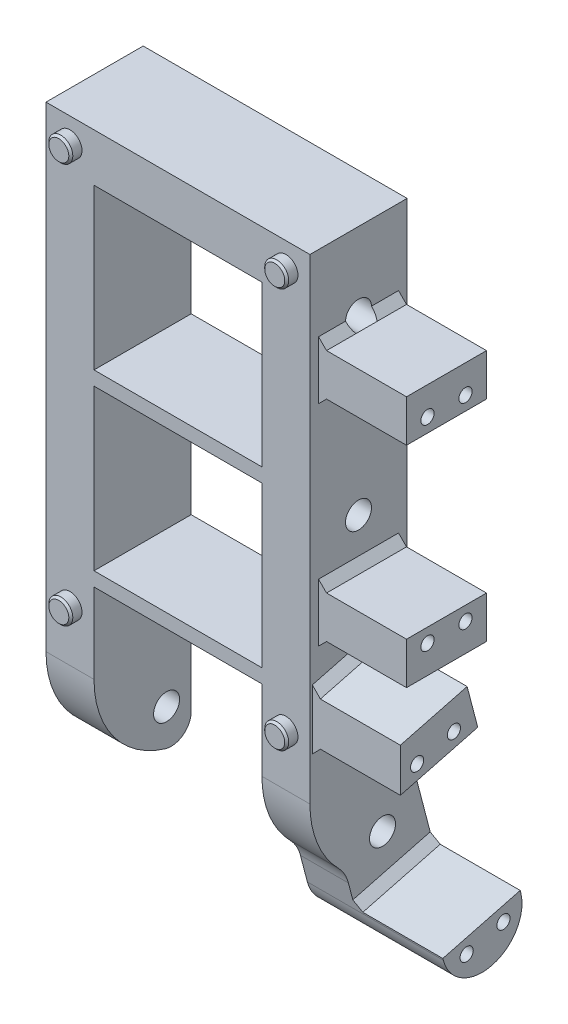
SolidWorks part; units mm, degrees
material "PBT General Purpose"
ref_plane "Front Plane" through (0, 0, 0) normal (0, 0, 1) x (1, 0, 0)
ref_plane "Top Plane" through (0, 0, 0) normal (0, 1, 0) x (1, 0, 0)
ref_plane "Right Plane" through (0, 0, 0) normal (1, 0, 0) x (0, 0, -1)
sketch "Sketch2" plane through (0, 0, 0) normal (0, 0, 1) x (1, 0, 0)
  line L0 (-33, 0) -> (33, 0)
  line L1 (33, 0) -> (33, -144)
  line L2 (33, -144) -> (21, -144)
  line L3 (21, -144) -> (21, -99)
  line L4 (21, -99) -> (-21, -99)
  line L5 (-21, -99) -> (-21, -144)
  line L6 (-21, -144) -> (-33, -144)
  line L7 (-33, -144) -> (-33, 0)
  line L8 (-21, -99) -> (-21, -95.5) construction
  line L9 (-21, -52) -> (21, -52)
  line L10 (-21, -52) -> (-21, -12)
  line L11 (-21, -12) -> (21, -12)
  line L12 (21, -52) -> (21, -12)
  line L13 (-21, -95.5) -> (21, -95.5)
  line L14 (-21, -95.5) -> (-21, -55.5)
  line L15 (-21, -55.5) -> (21, -55.5)
  line L16 (21, -95.5) -> (21, -55.5)
  line L17 (-21, -55.5) -> (-21, -52) construction
  line L18 (21, -52) -> (21, -55.5) construction
  line L19 (21, -95.5) -> (21, -99) construction
  dimension "D1" = 12
  dimension "D2" = 42
  dimension "D3" = 45
  dimension "D4" = 43.5
  dimension "D5" = 43.5
  dimension "D6" = 12
  dimension "D7" = 3.5
  dimension "D8" = 3.5
extrude "Boss-Extrude1" add sketch "Sketch2" along normal mid plane 24.3 contours L7 L0 L1 L2 L3 L4 L5 L6 | L10 L11 L12 L9 | L14 L15 L16 L13
sketch "Sketch3" plane through (0, 0, 0) normal (1, 0, 0) x (0, 0, -1)
  line L0 (-12.15, 0) -> (12.15, 0) construction
  circle A2 centre (0, -106) radius 3.25
  circle A3 centre (0, -62.5) radius 3.25
  circle A4 centre (0, -19) radius 3.25
  circle A5 centre (6, -134) radius 3.25
  dimension "D4" = 43.5
  dimension "D1" = 6.5
  dimension "D2" = 6.5
  dimension "D3" = 43.5
  dimension "D5" = 19
  dimension "D6" = 28
  dimension "D7" = 6
extrude "Cut-Extrude1" cut sketch "Sketch3" against normal through all both and the other way through all
fillet "Fillet1" radius 25 2 edges at (27, -144, 12.15) (-27, -144, 12.15)
fillet "Fillet2" radius 5 2 edges at (-27, -144, -12.15) (27, -144, -12.15)
sketch "Sketch4" plane through (0, 0, 12.15) normal (0, 0, -1) x (-1, 0, 0)
  line L5 (-33, -39.016) -> (-21, -39.016) construction
  line L6 (-27, -6) -> (27, -6) construction
  line L7 (-27, -6) -> (-27, -106) construction
  line L8 (-27, -106) -> (27, -106) construction
  line L9 (27, -6) -> (27, -106) construction
  line L10 (-33, 0) -> (-33, -138.1804) construction
  line L11 (-21, -52) -> (-21, -12) construction
  line L12 (0, -6) -> (0, 0) construction
  line L13 (33, 0) -> (-33, 0) construction
  line L14 (0, -6) -> (0, -12) construction
  line L15 (21, -12) -> (-21, -12) construction
  circle A0 centre (-27, -6) radius 3
  circle A1 centre (27, -6) radius 3
  circle A2 centre (27, -106) radius 3
  circle A3 centre (-27, -106) radius 3
  point P17 (-27, -39.016)
  dimension "D1" = 6
  dimension "D2" = 100
extrude "Boss-Extrude2" add sketch "Sketch4" against normal blind 2.8
chamfer "Chamfer1" distance 0.5 angle 45 4 edges at (-30, -106, 14.95) (24, -106, 14.95) (-30, -6, 14.95) (24, -6, 14.95)
ref_plane "Plane1" through (55, 0, 0) normal (1, 0, 0) x (0, 0, -1)
sketch "Sketch5" plane through (55, 0, 0) normal (1, 0, 0) x (0, 0, -1)
  line L0 (0, -62.5) -> (0, -76.89) construction
  line L1 (-4.75, -27.89) -> (4.75, -27.89) construction
  line L2 (-4.75, -27.89) -> (-4.75, -76.89) construction
  line L3 (-4.75, -76.89) -> (4.75, -76.89) construction
  line L4 (4.75, -27.89) -> (4.75, -76.89) construction
  line L5 (-7.3433, -101.7142) -> (5.0412, -149.1233) construction
  line L6 (-7.3433, -101.7142) -> (1.8483, -99.3131) construction
  line L7 (5.0412, -149.1233) -> (14.2328, -146.7223) construction
  line L8 (1.8483, -99.3131) -> (14.2328, -146.7223) construction
  line L9 (9.637, -147.9228) -> (6, -134) construction
  line L10 (12.15, 0) -> (12.15, -138.1804) construction
  circle A0 centre (6, -134) radius 3.25 construction
  point P11 (0, 0)
  point P14 (-7.8925, -103.9467)
  dimension "D1" = 9.5
  dimension "D2" = 49
  dimension "D3" = 14.39
  dimension "D4" = 165.36
sketch "Sketch6" plane through (55, 0, 0) normal (1, 0, 0) x (0, 0, -1)
  line L0 (4.75, -52.39) -> (-4.75, -52.39) construction
  line L1 (-10, -20.89) -> (10, -20.89)
  line L2 (-10, -20.89) -> (-10, -31.39)
  line L3 (-10, -31.39) -> (10, -31.39)
  line L4 (10, -20.89) -> (10, -31.39)
  line L5 (4.75, -27.89) -> (4.75, -76.89) construction
  line L6 (-4.75, -27.89) -> (-4.75, -76.89) construction
  line L7 (-10, -73.39) -> (10, -73.39)
  line L8 (10, -83.89) -> (10, -73.39)
  line L9 (-10, -83.89) -> (10, -83.89)
  line L10 (-10, -83.89) -> (-10, -73.39)
  line L12 (0, -62.5) -> (0, -76.89) construction
  line L13 (-4.75, -27.89) -> (4.75, -27.89) construction
  line L17 (-0.9229, -147.0639) -> (18.4277, -142.009)
  line L18 (1.7309, -157.223) -> (-0.9229, -147.0639)
  line L19 (1.7309, -157.223) -> (21.0815, -152.1681)
  line L21 (21.0815, -152.1681) -> (18.4277, -142.009)
  line L25 (9.637, -147.9228) -> (6, -134) construction
  line L26 (-1.151, -125.4188) -> (8.0405, -123.0177) construction
  line L27 (-7.3433, -101.7142) -> (5.0412, -149.1233) construction
  line L28 (1.8483, -99.3131) -> (14.2328, -146.7223) construction
  line L30 (-11.5382, -95.5752) -> (5.1586, -91.2135)
  line L31 (5.1586, -91.2135) -> (7.8124, -101.3726)
  line L32 (-11.5382, -106.4275) -> (7.8124, -101.3726)
  line L33 (-11.5382, -106.4275) -> (-11.5382, -95.5752)
  line L34 (5.0412, -149.1233) -> (14.2328, -146.7223) construction
  point P16 (0, -73.39)
  point P27 (8.7524, -144.5364)
  point P38 (-1.151, -149.0639)
  point P39 (18.4277, -144.009)
  point P40 (0, 0)
  point P41 (5.1586, -93.2135)
  point P42 (0, 0)
  dimension "D1" = 20
  dimension "D2" = 3.5
  dimension "D3" = 7
  dimension "D4" = 20
  dimension "D5" = 3.5
  dimension "D6" = 7
extrude "Boss-Extrude3" add sketch "Sketch6" against normal up to surface (22 mm away) up to face at (33, -134, -9.25)
sketch "Sketch8" plane through (33, 0, 0) normal (1, 0, 0) x (0, 0, -1)
  line L0 (-0.9229, -147.0639) -> (-3.2568, -138.1297)
  line L1 (12.15, 0) -> (12.15, -138.1804) construction
  line L2 (12.15, -117.9772) -> (12.15, -138.1804)
  line L3 (18.4277, -142.009) -> (12.15, -117.9772)
  line L4 (-0.9229, -147.0639) -> (1.7309, -157.223)
  line L5 (1.7309, -157.223) -> (21.0815, -152.1681)
  line L6 (21.0815, -152.1681) -> (18.4277, -142.009)
  line L7 (18.4277, -142.009) -> (-0.9229, -147.0639)
  line L8 (-0.9229, -147.0639) -> (1.7309, -157.223)
  line L9 (1.7309, -157.223) -> (21.0815, -152.1681)
  line L10 (21.0815, -152.1681) -> (18.4277, -142.009)
  arc A0 (5.725, -142.973) -> (12.15, -138.1804) centre (7.15, -138.1804) ccw construction
  arc A1 (-12.15, -119.0098) -> (5.725, -142.973) centre (12.85, -119.0098) ccw construction
  arc A2 (5.725, -142.973) -> (12.15, -138.1804) centre (7.15, -138.1804) ccw
  arc A3 (-3.2568, -138.1297) -> (5.725, -142.973) centre (12.85, -119.0098) ccw
  point P2 (12.15, -120.4299)
  dimension "D1" = 0
extrude "Boss-Extrude5" add sketch "Sketch8" against normal up to surface (12 mm away) up to face at (21, -137.25, -6)
sketch "Sketch7" plane through (55, 0, 0) normal (1, 0, 0) x (0, 0, -1)
  circle A0 centre (-4.75, -27.89) radius 1.65
  circle A1 centre (4.75, -27.89) radius 1.65
  circle A2 centre (-4.75, -76.89) radius 1.65
  circle A3 centre (4.75, -76.89) radius 1.65
  circle A4 centre (-7.3433, -101.7142) radius 1.65
  circle A5 centre (1.8483, -99.3131) radius 1.65
  circle A6 centre (5.0412, -149.1233) radius 1.65
  circle A7 centre (14.2328, -146.7223) radius 1.65
  dimension "D1" = 3.3
extrude "Cut-Extrude2" cut sketch "Sketch7" against normal blind 4
fillet "Fillet3" radius 10 4 edges at (38, -157.223, -1.7309) (38, -152.1681, -21.0815) (27, -117.9772, -12.15) (27, -138.1297, 3.2568)
chamfer "Chamfer3" distance 2 angle 45 9 edges at (33, -20.89, 6.322) (33, -20.89, -6.322) (33, -31.39, 0) (33, -73.39, 0) (33, -83.89, 0) (33, -93.3943, 3.1898) (33, -102.2136, -4.5931) (33, -105.2651, 7.0885) (33, -144.5364, -8.7524)
sketch "Sketch9" plane through (33, 0, 0) normal (1, 0, 0) x (0, 0, -1)
  circle A0 centre (0, -19) radius 3.25 construction
  circle A1 centre (0, -106) radius 3.25 construction
  circle A2 centre (0, -19) radius 3.25
  circle A3 centre (0, -106) radius 3.25
extrude "Cut-Extrude3" cut sketch "Sketch9" along normal blind 2
equation "\"frisbee spacing\"= 43.5"
equation "\"D4@Sketch2\"=\"frisbee spacing\""
equation "\"D5@Sketch2\"=\"frisbee spacing\""
equation "\"D4@Sketch3\"=\"frisbee spacing\""
equation "\"D3@Sketch3\"=\"frisbee spacing\""
